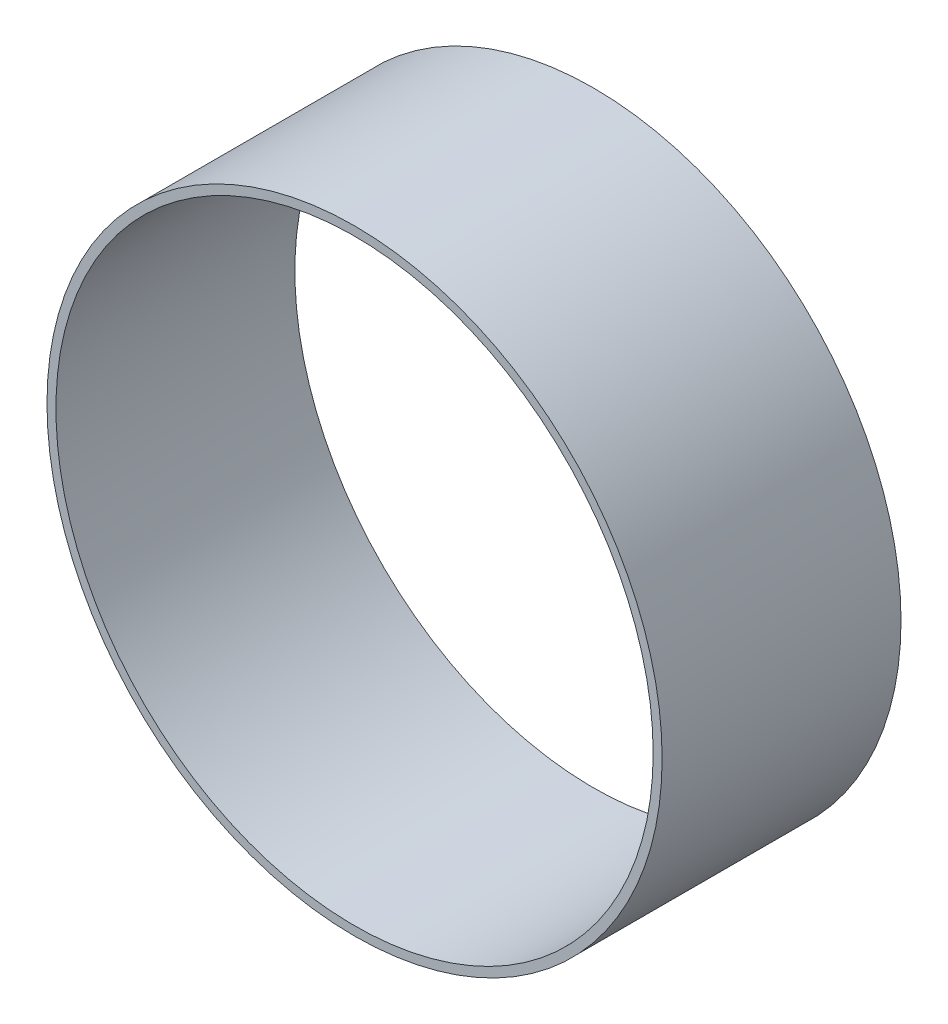
SolidWorks part; units mm, degrees
ref_plane "Front Plane" through (0, 0, 0) normal (0, 0, 1) x (1, 0, 0)
ref_plane "Top Plane" through (0, 0, 0) normal (0, 1, 0) x (1, 0, 0)
ref_plane "Right Plane" through (0, 0, 0) normal (1, 0, 0) x (0, 0, -1)
sketch "Sketch1" plane through (0, 0, 0) normal (0, 0, 1) x (1, 0, 0)
  circle A0 centre (0, 0) radius 65.405
  circle A1 centre (0, 0) radius 63.5
  dimension "D2" = 130.81
extrude "Boss-Extrude1" add sketch "Sketch1" along normal mid plane 50.8
equation "\"AIRFRAME_OD\"= 5.15in"
equation "\"AIRFRAME_ID\"= 5.00in"
equation "\"FLAT_T\"= 0.125in"
equation "\"NOSE_EXP_L\"= 27in"
equation "\"NOSE_SHOULDER_L\"= 5in"
equation "\"MAIN_L\"= 30in"
equation "\"RECO_COUP_L\"= 10in"
equation "\"RECO_SWITCH_L\"= 2in"
equation "\"DROGUE_L\"= 20in"
equation "\"ATS_FORE_COUP_L\"= 5.5in"
equation "\"ATS_AFT_COUP_L\"= 4.5in"
equation "\"LOWER_L\"= 30in"
equation "\"FIN_N\"= 4"
equation "\"CR_AFT_X\"= 0.5in"
equation "\"CR_FORE_X\"= 9.25in"
equation "\"D1@Sketch1\"=\"AIRFRAME_ID\""
equation "\"D2@Sketch1\"=\"AIRFRAME_OD\""
equation "\"D1@Boss-Extrude1\"=\"RECO_SWITCH_L\""
equation "\"FIN_ROOT\"= 5in"
equation "\"FIN_X\"= 0.75in"
equation "\"MOTOR_OD\"= 3.091in"
equation "\"MOTOR_ID\"= 3.00in"
equation "\"COUPLER_OD\"= 4.998in"
equation "\"COUPLER_ID\"= 4.88in"
equation "\"RECO_ROD_X\"= 3.5in"
equation "\"ATS_ROD_X\"= 3in"
equation "\"MOTOR_L\"= 14in"
equation "\"MOTOR_LOWER_X\"= 2in"
